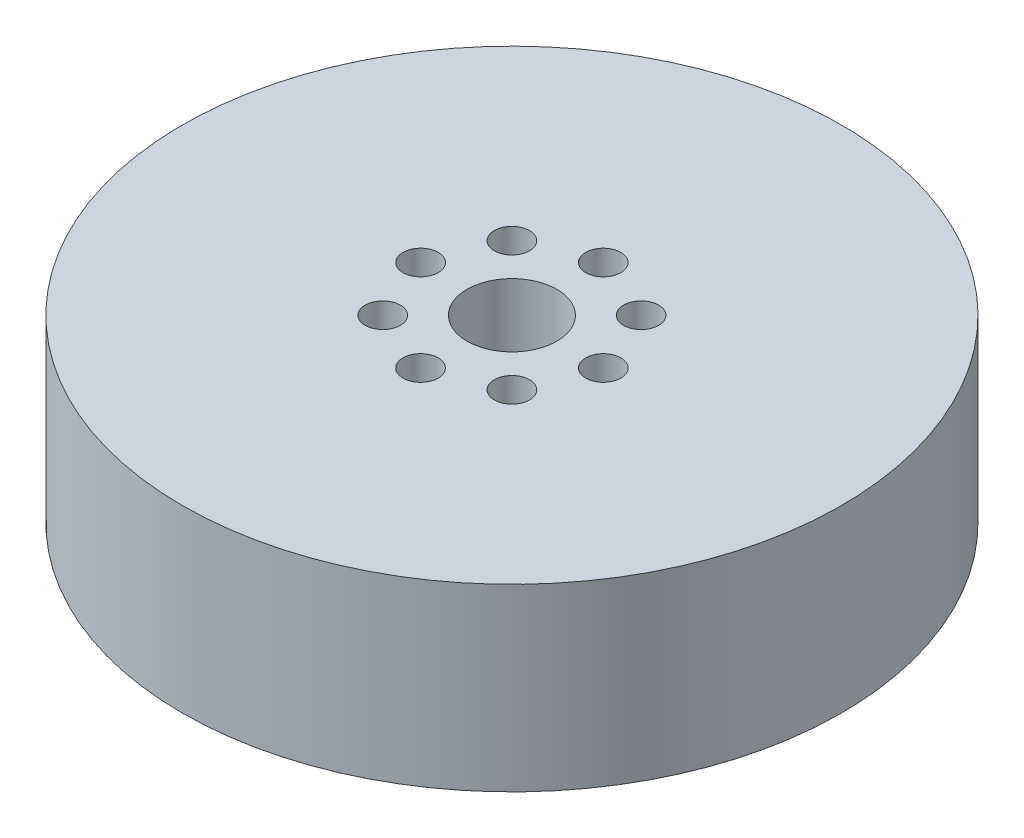
SolidWorks part; units mm, degrees
ref_plane "Front Plane" through (0, 0, 0) normal (0, 0, 1) x (1, 0, 0)
ref_plane "Top Plane" through (0, 0, 0) normal (0, 1, 0) x (1, 0, 0)
ref_plane "Right Plane" through (0, 0, 0) normal (1, 0, 0) x (0, 0, -1)
sketch "Sketch1" plane through (0, 0, 0) normal (0, 1, 0) x (1, 0, 0)
  circle A0 centre (0, 0) radius 55
  dimension "FLANGE_OD" = 110
extrude "Boss-Extrude1" add sketch "Sketch1" along normal blind 30
sketch "Sketch2" plane through (0, 0, 0) normal (0, 1, 0) x (1, 0, 0)
  circle A0 centre (0, 0) radius 7.5
  dimension "BORE_D" = 15
extrude "Cut-Extrude1" cut sketch "Sketch2" along normal through all
sketch "Sketch3" plane through (0, 30, 0) normal (0, 1, 0) x (1, 0, 0)
  circle A0 centre (0, 0) radius 15.2428 construction
  circle A1 centre (-15.2428, 0) radius 2.9339
  dimension "BOLT_D" = 5.8679
  dimension "BOLT_PCD" = 30.4855
extrude "Cut-Extrude2" cut sketch "Sketch3" against normal blind 23.397
pattern_circular "CirPattern1" count 8 over 360 about axis through (0, 0, 0) along (0, 1, 0) of "Cut-Extrude2"
